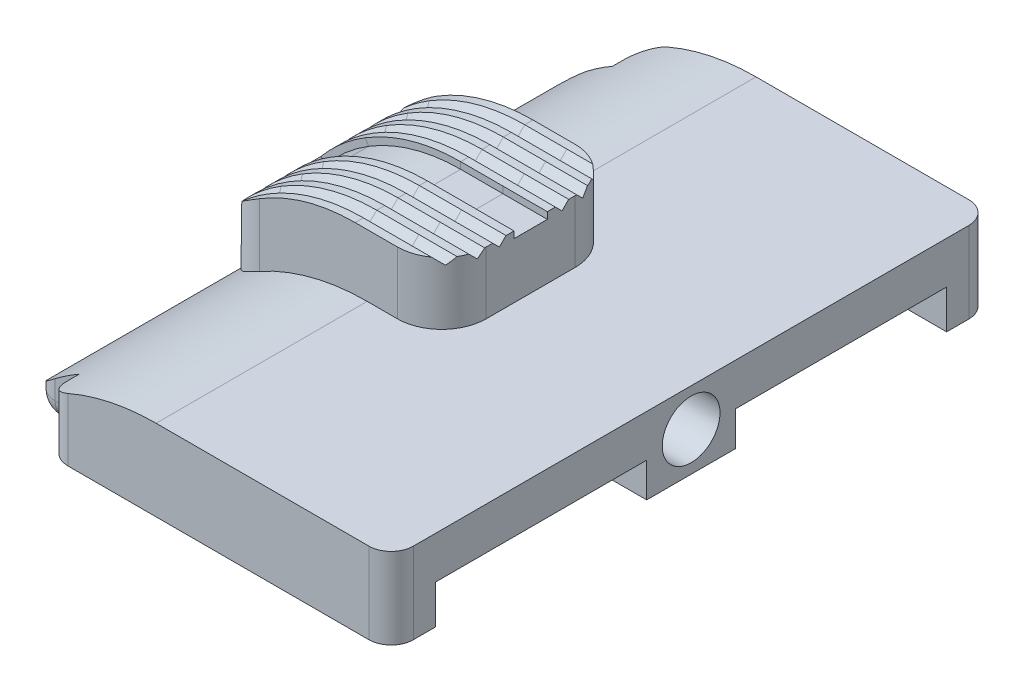
SolidWorks part; units mm, degrees
ref_plane "Front Plane" through (0, 0, 0) normal (0, 0, 1) x (1, 0, 0)
ref_plane "Top Plane" through (0, 0, 0) normal (0, 1, 0) x (1, 0, 0)
ref_plane "Right Plane" through (0, 0, 0) normal (1, 0, 0) x (0, 0, -1)
sketch "Sketch2" plane through (0, 0, 0) normal (0, 0, 1) x (1, 0, 0)
  line L1 (-4.405, 0.975) -> (4.405, 0.975)
  line L2 (-4.405, 0.975) -> (-4.405, -0.975)
  line L3 (-4.405, -0.975) -> (4.405, -0.975)
  line L4 (4.405, 0.975) -> (4.405, -0.975)
  line L5 (-4.405, 0.975) -> (4.405, -0.975) construction
  line L6 (-4.405, -0.975) -> (4.405, 0.975) construction
  arc A0 (-4.405, -0.475) -> (-0.884, 0.975) centre (-0.884, -4.025) cw
  point P0 (0, 0)
  dimension "D2" = 5
  dimension "D1" = 1.45
  dimension "D3" = 1.95
  dimension "D4" = 8.81
extrude "Boss-Extrude1" add sketch "Sketch2" along normal mid plane 12 contours A0 L2 L3 L4 L1 region at (0.3621, -0.0564, 0)
sketch "Sketch3" plane through (0, 0, 0) normal (0, 0, 1) x (1, 0, 0)
  line L0 (-4.405, 0.1724) -> (-4.405, -0.4336) construction
  line L2 (-4.405, 0.52) -> (-4.405, -0.4336) construction
  line L4 (-4.405, 0.7745) -> (-4.405, -0.475)
  line L5 (-0.884, 0.975) -> (0.895, 0.975)
  line L7 (0.895, 2.225) -> (-1.155, 2.225)
  line L8 (-4.305, 0.8994) -> (-4.305, -0.3785)
  line L9 (-4.305, 0.52) -> (-4.305, -0.4336) construction
  line L10 (0.895, 0.975) -> (0.895, 2.225) construction
  line L11 (0.895, 0.975) -> (0.895, 2.375)
  line L12 (0.795, 0.975) -> (0.795, 2.375)
  line L13 (0.795, 0.975) -> (0.795, 2.225) construction
  line L14 (0.895, 2.375) -> (-1.155, 2.375)
  line L16 (-0.884, 0.975) -> (4.405, 0.975) construction
  line L17 (-4.405, -0.475) -> (-4.405, -0.975) construction
  arc A3 (-1.155, 2.225) -> (-4.405, 0.52) centre (-1.155, -1.725) ccw
  arc A4 (-0.884, 0.975) -> (-4.405, -0.475) centre (-0.884, -4.025) ccw construction
  arc A5 (-0.884, 0.975) -> (-4.405, -0.475) centre (-0.884, -4.025) ccw
  arc A6 (-1.155, 2.375) -> (-4.405, 0.7745) centre (-1.155, -1.725) ccw
  arc A7 (-1.155, 2.375) -> (-4.5284, 0.6052) centre (-1.155, -1.725) ccw construction
  dimension "D5" = 3.95
  dimension "D8" = 0.15
  dimension "D3" = 5.3
  dimension "D4" = 1.25
  dimension "D6" = 1.155
  dimension "D7" = 1.725
  dimension "D1" = 0.1
  dimension "D2" = 0.1
extrude "Boss-Extrude2" add sketch "Sketch3" along normal mid plane 4 contours L7 A3 L8 L5 | A3 L7 L12 L8 region at (-2.8714, 1.9391, 0) region at (-1.7263, 1.3254, 0)
fillet "Fillet1" radius 1 4 edges at (0.795, 1.675, -2) (0.795, 1.675, 2) (-4.305, 0.2604, 2) (-4.305, 0.2604, -2)
sketch "Sketch4" plane through (0, 0, 2) normal (0, 0, 1) x (1, 0, 0)
  line L9 (0.795, 2.375) -> (-0.205, 2.375) construction
  line L10 (-0.205, 2.375) -> (-1.155, 2.375) construction
  line L11 (0.795, 2.375) -> (-0.205, 2.375)
  line L12 (-0.205, 2.375) -> (-1.155, 2.375)
  arc A1 (-1.155, 2.375) -> (-3.305, 1.7661) centre (-1.155, -1.725) ccw construction
  arc A2 (-3.305, 1.7661) -> (-4.305, 0.8994) centre (-1.155, -1.725) ccw construction
  arc A3 (-1.155, 2.375) -> (-3.305, 1.7661) centre (-1.155, -1.725) ccw
  arc A4 (-3.305, 1.7661) -> (-4.305, 0.8994) centre (-1.155, -1.725) ccw
  point P4 (0.5746, 2.6015)
  point P10 (0.795, 2.375)
  point P13 (-4.305, 0.8994)
sketch "Sketch5" plane through (0.795, 0, 0) normal (1, 0, 0) x (0, 0, -1)
  line L0 (0, 2.375) -> (0, 0.6417) construction
  line L2 (-1.815, 2.375) -> (-1.665, 2.225)
  line L4 (-0.375, 2.375) -> (-0.375, 2.225)
  line L5 (-0.375, 2.225) -> (0.375, 2.225)
  line L6 (0.375, 2.375) -> (0.375, 2.225)
  line L7 (2, 2.375) -> (1, 2.375) construction
  line L8 (-1.665, 2.225) -> (-1.515, 2.375)
  line L9 (-1.515, 2.375) -> (-1.335, 2.375)
  line L10 (-1.335, 2.375) -> (-1.185, 2.225)
  line L11 (-1.185, 2.225) -> (-1.035, 2.375)
  line L12 (-1.035, 2.375) -> (-0.855, 2.375)
  line L13 (-0.855, 2.375) -> (-0.705, 2.225)
  line L14 (-0.705, 2.225) -> (-0.555, 2.375)
  line L15 (-0.555, 2.375) -> (-0.375, 2.375)
  line L16 (-1.665, 2.225) -> (-1.185, 2.225) construction
  line L17 (-1.185, 2.225) -> (-0.705, 2.225) construction
  line L18 (-0.705, 2.225) -> (-0.375, 2.225) construction
  line L19 (1.185, 2.225) -> (0.705, 2.225) construction
  line L20 (1.665, 2.225) -> (1.185, 2.225) construction
  line L21 (0.705, 2.225) -> (0.555, 2.375)
  line L22 (0.855, 2.375) -> (0.705, 2.225)
  line L23 (1.035, 2.375) -> (0.855, 2.375)
  line L24 (1.185, 2.225) -> (1.035, 2.375)
  line L25 (1.335, 2.375) -> (1.185, 2.225)
  line L26 (1.515, 2.375) -> (1.335, 2.375)
  line L27 (1.665, 2.225) -> (1.515, 2.375)
  line L28 (1.815, 2.375) -> (1.665, 2.225)
  line L29 (-1.815, 2.375) -> (-1.815, 2.475)
  line L30 (-1.815, 2.475) -> (1.815, 2.475)
  line L31 (1.815, 2.475) -> (1.815, 2.375)
  line L32 (0.375, 2.375) -> (0.555, 2.375)
  line L35 (-1.815, 2.375) -> (1.815, 2.375) construction
  point P2 (0, 0)
  point P11 (0, 0)
  point P12 (0, 0)
  point P13 (0, 0)
  point P21 (0, 0)
  point P33 (0, 0)
  point P36 (0, 0)
  dimension "D1" = 0.15
  dimension "D2" = 0.75
  dimension "D3" = 0.18
  dimension "D4" = 0.18
  dimension "D5" = 0.15
  dimension "D6" = 0.25
sweep "Cut-Sweep1" cut profiles "Sketch5" path "Sketch4"
sketch "Sketch7" plane through (0, 0, 0) normal (0, 0, 1) x (1, 0, 0)
  line L0 (4.405, -0.975) -> (4.405, 0.975) construction
  line L1 (-3.365, -0.975) -> (4.405, -0.975) construction
  line L2 (-3.365, 0.316) -> (-3.365, -0.975) construction
  line L3 (4.405, 0.975) -> (-0.884, 0.975) construction
  line L4 (4.405, -0.975) -> (4.405, 0.975)
  line L5 (-3.365, -0.975) -> (4.405, -0.975)
  line L6 (-3.365, 0.316) -> (-3.365, -0.975)
  line L7 (4.405, 0.975) -> (-0.884, 0.975)
  arc A0 (-0.884, 0.975) -> (-3.365, 0.316) centre (-0.884, -4.025) ccw construction
  arc A1 (-0.884, 0.975) -> (-3.365, 0.316) centre (-0.884, -4.025) ccw
extrude "Boss-Extrude3" add sketch "Sketch7" along normal mid plane 13.5
fillet "Fillet2" radius 0.5 6 edges at (4.405, 0, 6.75) (-3.365, -0.3295, 6.75) (4.405, 0, -6.75) (-4.405, -0.725, 6) (-4.405, -0.725, -6) (-3.365, -0.3295, -6.75)
sketch "Sketch6" plane through (4.405, 0, 0) normal (1, 0, 0) x (0, 0, -1)
  line L0 (-6.25, 0.975) -> (6.25, 0.975) construction
  line L1 (0, 0) -> (0, -1.5692) construction
  circle A0 centre (0, 0.125) radius 0.65
  point P2 (0, -0.525)
  dimension "D2" = 1.3
  dimension "D1" = 1.5
extrude "Cut-Extrude1" cut sketch "Sketch6" against normal blind 2.5
sketch "Sketch8" plane through (0, -0.975, 0) normal (0, -1, 0) x (1, 0, 0)
  line L0 (-2.865, 6.75) -> (3.905, 6.75) construction
  line L1 (0.905, 6.75) -> (4.405, 6.75)
  line L2 (0.905, 6.75) -> (0.905, -6.75)
  line L3 (0.905, -6.75) -> (4.405, -6.75)
  line L4 (4.405, 6.75) -> (4.405, -6.75)
  line L5 (4.405, 6.25) -> (4.405, -6.25) construction
  line L6 (-2.865, -6.75) -> (3.905, -6.75) construction
  line L7 (0.905, 5.75) -> (4.405, 5.75)
  line L8 (0.905, 1) -> (4.405, 1)
  line L9 (0.905, 1) -> (0.905, -1)
  line L10 (0.905, -1) -> (4.405, -1)
  line L11 (4.405, 1) -> (4.405, -1)
  line L12 (0.905, -5.75) -> (4.405, -5.75)
  dimension "D1" = 3.5
  dimension "D2" = 1
  dimension "D3" = 2
  dimension "D4" = 1
  dimension "D5" = 1
fillet "Fillet3" radius 0.5 5 edges at (-3.635, -0.975, 6) (-4.2586, -0.975, 5.8536) (-3.635, -0.975, -6) (-4.2586, -0.975, -5.8536) (-4.405, -0.975, 0)
extrude "Cut-Extrude2" cut sketch "Sketch8" against normal blind 1 contours L2 L12 L4 L10 | L2 L8 L4 L7 region at (2.655, -0.975, 3.375) region at (2.655, -0.975, -3.375)
sketch "Sketch9" plane through (0, 0, 6.75) normal (0, 0, 1) x (1, 0, 0)
  line L0 (4.405, 0.975) -> (4.405, -0.975) construction
  line L1 (-4.405, -0.975) -> (4.405, -0.975)
  line L2 (-4.405, -0.975) -> (-4.405, -0.85)
  line L3 (-4.405, -0.85) -> (4.405, -0.85)
  line L4 (4.405, -0.975) -> (4.405, -0.85)
  line L5 (-2.865, -0.975) -> (3.905, -0.975) construction
  dimension "D1" = 0.125
extrude "Cut-Extrude3" cut sketch "Sketch9" against normal through all
sketch "Sketch10" plane through (0, -0.85, 0) normal (0, -1, 0) x (1, 0, 0)
  line L1 (4.405, 1) -> (0.905, 1)
  line L2 (4.405, 1) -> (4.405, -1)
  line L3 (4.405, -1) -> (0.905, -1)
  line L4 (0.905, 1) -> (0.905, -1)
extrude "Cut-Extrude4" cut sketch "Sketch10" against normal blind 0.1
